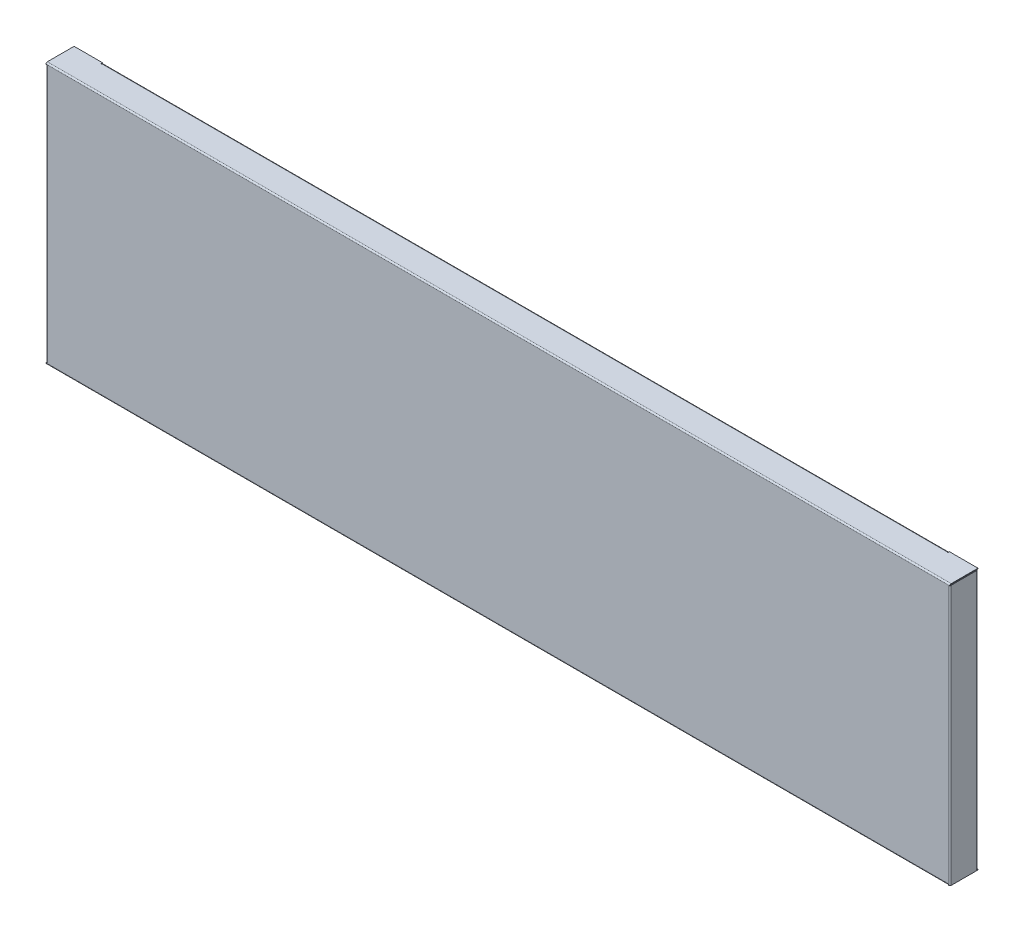
SolidWorks part; units mm, degrees
note: The reader was unsure of these and kept them because the rebuilt part matched: flange length of "Edge-Flange1", "Edge-Flange2", "Edge-Flange3", "Edge-Flange4", "Edge-Flange5", "Edge-Flange6", "Edge-Flange7", "Edge-Flange8".
ref_plane "Front Plane" through (0, 0, 0) normal (0, 0, 1) x (1, 0, 0)
ref_plane "Top Plane" through (0, 0, 0) normal (0, 1, 0) x (1, 0, 0)
ref_plane "Right Plane" through (0, 0, 0) normal (1, 0, 0) x (0, 0, -1)
sketch "Sketch1" plane through (0, 0, 0) normal (0, 0, 1) x (1, 0, 0)
  line L1 (-482.5, -139.5) -> (482.5, -139.5)
  line L2 (-482.5, -139.5) -> (-482.5, 139.5)
  line L3 (-482.5, 139.5) -> (482.5, 139.5)
  line L4 (482.5, -139.5) -> (482.5, 139.5)
  line L5 (-482.5, -139.5) -> (482.5, 139.5) construction
  line L6 (-482.5, 139.5) -> (482.5, -139.5) construction
  point P0 (0, 0)
  dimension "D1" = 965
  dimension "D2" = 279
base flange "Base-Flange1" sketch "Sketch1" thickness 0.7366 reverse thickness direction no parameters "D1"=0.7366
edge flange "Edge-Flange1" sketch "Sketch8" flange angle 90 flange length 30 flange position material inside bend radius 0.7366 thickness 0.7366 relief rectangular parameters "D6"=10
sketch "Sketch8" plane through (0, 139.5, -0.7366) normal (0, 1, 0) x (1, 0, 0)
  line L0 (482.5, 0) -> (-482.5, 0) construction
  line L1 (482.5, 0) -> (-482.5, 0)
  line L2 (-482.5, 0) -> (-482.5, 29.2634)
  line L3 (-482.5, 29.2634) -> (482.5, 29.2634)
  line L4 (482.5, 29.2634) -> (482.5, 0)
bend "EdgeBend1" bend radius 0.7366 bend angle 90 parameters "D5"=1
edge flange "Edge-Flange2" sketch "Sketch11" flange angle 90 flange length 30 flange position material inside bend radius 0.7366 thickness 0.7366 relief none parameters "D6"=10
sketch "Sketch11" plane through (482.5, 0, -0.7366) normal (1, 0, 0) x (0, -1, 0)
  line L0 (139.5, 0) -> (-138.0268, 0) construction
  line L1 (139.5, 0) -> (-138.0268, 0)
  line L2 (-138.0268, 0) -> (-138.0268, 29.2634)
  line L3 (-138.0268, 29.2634) -> (139.5, 29.2634)
  line L4 (139.5, 29.2634) -> (139.5, 0)
bend "EdgeBend2" bend radius 0.7366 bend angle 90 parameters "D5"=2
edge flange "Edge-Flange3" sketch "Sketch14" flange angle 90 flange length 30 flange position material inside bend radius 0.7366 thickness 0.7366 relief none parameters "D6"=10
sketch "Sketch14" plane through (0, -139.5, -0.7366) normal (0, -1, 0) x (-1, 0, 0)
  line L0 (482.5, 0) -> (-481.0268, 0) construction
  line L1 (482.5, 0) -> (-481.0268, 0)
  line L2 (-481.0268, 0) -> (-481.0268, 29.2634)
  line L3 (-481.0268, 29.2634) -> (482.5, 29.2634)
  line L4 (482.5, 29.2634) -> (482.5, 0)
bend "EdgeBend3" bend radius 0.7366 bend angle 90 parameters "D5"=3
edge flange "Edge-Flange4" sketch "Sketch17" flange angle 90 flange length 30 flange position material inside bend radius 0.7366 thickness 0.7366 relief none parameters "D6"=10
sketch "Sketch17" plane through (-482.5, 0, -0.7366) normal (-1, 0, 0) x (0, 1, 0)
  line L0 (138.0268, 0) -> (-138.0268, 0) construction
  line L1 (138.0268, 0) -> (-138.0268, 0)
  line L2 (-138.0268, 0) -> (-138.0268, 29.2634)
  line L3 (-138.0268, 29.2634) -> (138.0268, 29.2634)
  line L4 (138.0268, 29.2634) -> (138.0268, 0)
bend "EdgeBend4" bend radius 0.7366 bend angle 90 parameters "D5"=4
edge flange "Edge-Flange5" sketch "Sketch20" flange angle 90 flange length 30 flange position material inside bend radius 0.7366 thickness 0.7366 relief rectangular parameters "D6"=10
sketch "Sketch20" plane through (0, -138.7634, -30) normal (0, 0, -1) x (-1, 0, 0)
  line L0 (482.5, 0) -> (-481.0268, 0) construction
  line L1 (451.5634, 0) -> (-451.5634, 0)
  line L2 (-451.5634, 0) -> (-451.5634, 29.2634)
  line L3 (-451.5634, 29.2634) -> (451.5634, 29.2634)
  line L4 (451.5634, 29.2634) -> (451.5634, 0)
  line L5 (481.7634, 276.7902) -> (481.7634, 0.7366) construction
  line L6 (-481.7634, -0.7366) -> (-481.7634, 276.7902) construction
  dimension "D1" = 30.2
  dimension "D2" = 29.2634
  dimension "D3" = 30.2
bend "EdgeBend5" bend radius 0.7366 bend angle 90 parameters "D5"=5
edge flange "Edge-Flange6" sketch "Sketch23" flange angle 90 flange length 30 flange position material inside bend radius 0.7366 thickness 0.7366 relief rectangular parameters "D6"=10
sketch "Sketch23" plane through (0, 138.7634, -30) normal (0, 0, -1) x (1, 0, 0)
  line L0 (482.5, 0) -> (-482.5, 0) construction
  line L1 (451.5634, 0) -> (-451.5634, 0)
  line L2 (-451.5634, 0) -> (-451.5634, 29.2634)
  line L3 (-451.5634, 29.2634) -> (451.5634, 29.2634)
  line L4 (451.5634, 29.2634) -> (451.5634, 0)
  line L5 (-481.7634, 0.7366) -> (-481.7634, 276.7902) construction
  line L6 (481.7634, 278.2634) -> (481.7634, 0.7366) construction
  dimension "D1" = 30.2
  dimension "D2" = 30.2
bend "EdgeBend6" bend radius 0.7366 bend angle 90 parameters "D5"=6
edge flange "Edge-Flange7" sketch "Sketch26" flange angle 90 flange length 30 flange position material inside bend radius 0.7366 thickness 0.7366 relief rectangular parameters "D6"=10
sketch "Sketch26" plane through (481.7634, 0, -30) normal (0, 0, 1) x (0, 1, 0)
  line L1 (138.0268, 0) -> (-139.5, 0) construction
  line L2 (-138.5634, 0) -> (-138.5634, 29.2634)
  line L3 (-138.5634, 29.2634) -> (138.0634, 29.2634)
  line L4 (138.0634, 29.2634) -> (138.0634, 0)
  line L5 (138.0634, 0) -> (-138.5634, 0)
  line L6 (138.7634, -0.7366) -> (138.7634, 29.8317) construction
  line L7 (-138.7634, 29.8317) -> (-138.7634, 0.7366) construction
  dimension "D1" = 0.7
  dimension "D2" = 0.2
bend "EdgeBend7" bend radius 0.7366 bend angle 90 parameters "D5"=7
edge flange "Edge-Flange8" sketch "Sketch29" flange angle 90 flange length 30 flange position material inside bend radius 0.7366 thickness 0.7366 relief rectangular parameters "D6"=10
sketch "Sketch29" plane through (-481.7634, 0, -30) normal (0, 0, -1) x (0, 1, 0)
  line L0 (138.0268, 0) -> (-138.0268, 0) construction
  line L1 (138.0268, 0) -> (-138.0268, 0)
  line L2 (-138.0268, 0) -> (-138.0268, 29.2634)
  line L3 (-138.0268, 29.2634) -> (138.0268, 29.2634)
  line L4 (138.0268, 29.2634) -> (138.0268, 0)
bend "EdgeBend8" bend radius 0.7366 bend angle 90 parameters "D5"=8
sketch "Bend-Lines1" [suppressed] plane through (0, 0, 0) normal (0, 1, 0) x (1, 0, 0)
sketch "Bounding-Box1" [suppressed] plane through (0, 0, 0) normal (0, 1, 0) x (1, 0, 0)
sheet metal parameters "Sheet-Metal1" thickness 0.7366 parameters "D1"=0.7366
flat pattern "Flat-Pattern1" [suppressed]
sketch "Bend-Lines2" plane through (0, 0, 0) normal (0, 1, 0) x (1, 0, 0)
sketch3d "Bounding-Box2" [suppressed]
  line L0 (482.65, -190, 0) -> (-482.65, -190, 0) construction
  line L1 (482.65, 190, 0) -> (-482.65, 190, 0) construction
  line L2 (482.65, -190, 0) -> (482.65, 190, 0) construction
  line L3 (-482.65, -190, 0) -> (-482.65, 190, 0) construction
sheet metal parameters "Sheet-Metal2" thickness 0.7366 parameters "D1"=0.7366
flat pattern "Flat-Pattern1"
sketch "Bend-Lines2" plane through (0, 0, 0) normal (0, 0, 1) x (1, 0, 0)
  line L0 (482.65, 189.3946) -> (-482.65, 189.3946) construction
  line L1 (482.65, 189.3946) -> (-482.65, 189.3946) construction
sketch3d "Bounding-Box2" [suppressed]
  line L0 (-482.65, -190, 0) -> (482.65, -190, 0) construction
  line L1 (-482.65, 218.7892, 0) -> (482.65, 218.7892, 0) construction
  line L2 (-482.65, -190, 0) -> (-482.65, 218.7892, 0) construction
  line L3 (482.65, -190, 0) -> (482.65, 218.7892, 0) construction
bend of the flat pattern "Flatten-<EdgeBend1>1"
sheet metal parameters "Sheet-Metal3" thickness 0.7366 parameters "D1"=0.7366
flat pattern "Flat-Pattern1"
sketch "Bend-Lines2" plane through (0, 0, 0) normal (0, 0, 1) x (1, 0, 0)
  line L0 (482.65, 189.3946) -> (-482.65, 189.3946) construction
  line L1 (482.65, 189.3946) -> (-482.65, 189.3946) construction
  line L2 (482.0446, -190) -> (482.0446, 188.5268) construction
  line L3 (482.0446, -190) -> (482.0446, 188.5268) construction
sketch3d "Bounding-Box2" [suppressed]
  line L0 (-482.65, -190, 0) -> (511.4392, -190, 0) construction
  line L1 (-482.65, 218.7892, 0) -> (511.4392, 218.7892, 0) construction
  line L2 (-482.65, -190, 0) -> (-482.65, 218.7892, 0) construction
  line L3 (511.4392, -190, 0) -> (511.4392, 218.7892, 0) construction
bend of the flat pattern "Flatten-<EdgeBend1>1"
bend of the flat pattern "Flatten-<EdgeBend2>1"
sheet metal parameters "Sheet-Metal4" thickness 0.7366 parameters "D1"=0.7366
flat pattern "Flat-Pattern1"
sketch "Bend-Lines2" plane through (0, 0, 0) normal (0, 0, 1) x (1, 0, 0)
  line L0 (482.65, 189.3946) -> (-482.65, 189.3946) construction
  line L1 (482.65, 189.3946) -> (-482.65, 189.3946) construction
  line L2 (482.0446, -190) -> (482.0446, 188.5268) construction
  line L3 (482.0446, -190) -> (482.0446, 188.5268) construction
  line L4 (-482.65, -189.3946) -> (481.1768, -189.3946) construction
  line L5 (-482.65, -189.3946) -> (481.1768, -189.3946) construction
sketch3d "Bounding-Box2" [suppressed]
  line L0 (-482.65, -218.7892, 0) -> (511.4392, -218.7892, 0) construction
  line L1 (-482.65, 218.7892, 0) -> (511.4392, 218.7892, 0) construction
  line L2 (-482.65, -218.7892, 0) -> (-482.65, 218.7892, 0) construction
  line L3 (511.4392, -218.7892, 0) -> (511.4392, 218.7892, 0) construction
bend of the flat pattern "Flatten-<EdgeBend1>1"
bend of the flat pattern "Flatten-<EdgeBend2>1"
bend of the flat pattern "Flatten-<EdgeBend3>1"
sheet metal parameters "Sheet-Metal5" thickness 0.7366 parameters "D1"=0.7366
flat pattern "Flat-Pattern1"
sketch "Bend-Lines2" plane through (0, 0, 0) normal (0, 0, 1) x (1, 0, 0)
  line L0 (482.65, 189.3946) -> (-482.65, 189.3946) construction
  line L1 (482.65, 189.3946) -> (-482.65, 189.3946) construction
  line L2 (482.0446, -190) -> (482.0446, 188.5268) construction
  line L3 (482.0446, -190) -> (482.0446, 188.5268) construction
  line L4 (-482.65, -189.3946) -> (481.1768, -189.3946) construction
  line L5 (-482.65, -189.3946) -> (481.1768, -189.3946) construction
  line L6 (-482.0446, 188.5268) -> (-482.0446, -188.5268) construction
  line L7 (-482.0446, 188.5268) -> (-482.0446, -188.5268) construction
sketch3d "Bounding-Box2" [suppressed]
  line L0 (-511.4392, -218.7892, 0) -> (511.4392, -218.7892, 0) construction
  line L1 (-511.4392, 218.7892, 0) -> (511.4392, 218.7892, 0) construction
  line L2 (-511.4392, -218.7892, 0) -> (-511.4392, 218.7892, 0) construction
  line L3 (511.4392, -218.7892, 0) -> (511.4392, 218.7892, 0) construction
bend of the flat pattern "Flatten-<EdgeBend1>1"
bend of the flat pattern "Flatten-<EdgeBend2>1"
bend of the flat pattern "Flatten-<EdgeBend3>1"
bend of the flat pattern "Flatten-<EdgeBend4>1"
sheet metal parameters "Sheet-Metal6" thickness 0.7366 parameters "D1"=0.7366
flat pattern "Flat-Pattern1"
sketch "Bend-Lines2" plane through (0, 0, 0) normal (0, 0, 1) x (1, 0, 0)
  line L0 (482.65, 189.3946) -> (-482.65, 189.3946) construction
  line L1 (482.65, 189.3946) -> (-482.65, 189.3946) construction
  line L2 (482.0446, -190) -> (482.0446, 188.5268) construction
  line L3 (482.0446, -190) -> (482.0446, 188.5268) construction
  line L4 (-482.65, -189.3946) -> (481.1768, -189.3946) construction
  line L5 (-482.65, -189.3946) -> (481.1768, -189.3946) construction
  line L6 (-482.0446, 188.5268) -> (-482.0446, -188.5268) construction
  line L7 (-482.0446, 188.5268) -> (-482.0446, -188.5268) construction
  line L8 (-482.65, -218.1838) -> (481.1768, -218.1838) construction
  line L9 (-482.65, -218.1838) -> (481.1768, -218.1838) construction
sketch3d "Bounding-Box2" [suppressed]
  line L0 (-511.4392, -247.5783, 0) -> (511.4392, -247.5783, 0) construction
  line L1 (-511.4392, 218.7892, 0) -> (511.4392, 218.7892, 0) construction
  line L2 (-511.4392, -247.5783, 0) -> (-511.4392, 218.7892, 0) construction
  line L3 (511.4392, -247.5783, 0) -> (511.4392, 218.7892, 0) construction
bend of the flat pattern "Flatten-<EdgeBend1>1"
bend of the flat pattern "Flatten-<EdgeBend2>1"
bend of the flat pattern "Flatten-<EdgeBend3>1"
bend of the flat pattern "Flatten-<EdgeBend4>1"
bend of the flat pattern "Flatten-<EdgeBend5>1"
sheet metal parameters "Sheet-Metal7" thickness 0.7366 parameters "D1"=0.7366
flat pattern "Flat-Pattern1"
sketch "Bend-Lines2" plane through (0, 0, 0) normal (0, 0, 1) x (1, 0, 0)
  line L0 (482.65, 189.3946) -> (-482.65, 189.3946) construction
  line L1 (482.65, 189.3946) -> (-482.65, 189.3946) construction
  line L2 (482.0446, -190) -> (482.0446, 188.5268) construction
  line L3 (482.0446, -190) -> (482.0446, 188.5268) construction
  line L4 (-482.65, -189.3946) -> (481.1768, -189.3946) construction
  line L5 (-482.65, -189.3946) -> (481.1768, -189.3946) construction
  line L6 (-482.0446, 188.5268) -> (-482.0446, -188.5268) construction
  line L7 (-482.0446, 188.5268) -> (-482.0446, -188.5268) construction
  line L8 (-451.7134, -218.1838) -> (451.7134, -218.1838) construction
  line L9 (-451.7134, -218.1838) -> (451.7134, -218.1838) construction
  line L10 (451.7134, 218.1838) -> (-451.7134, 218.1838) construction
  line L11 (451.7134, 218.1838) -> (-451.7134, 218.1838) construction
sketch3d "Bounding-Box2" [suppressed]
  line L0 (-511.4392, -247.5783, 0) -> (511.4392, -247.5783, 0) construction
  line L1 (-511.4392, 247.5783, 0) -> (511.4392, 247.5783, 0) construction
  line L2 (-511.4392, -247.5783, 0) -> (-511.4392, 247.5783, 0) construction
  line L3 (511.4392, -247.5783, 0) -> (511.4392, 247.5783, 0) construction
bend of the flat pattern "Flatten-<EdgeBend1>1"
bend of the flat pattern "Flatten-<EdgeBend2>1"
bend of the flat pattern "Flatten-<EdgeBend3>1"
bend of the flat pattern "Flatten-<EdgeBend4>1"
bend of the flat pattern "Flatten-<EdgeBend5>1"
bend of the flat pattern "Flatten-<EdgeBend6>1"
sheet metal parameters "Sheet-Metal8" thickness 0.7366 parameters "D1"=0.7366
flat pattern "Flat-Pattern1"
sketch "Bend-Lines2" plane through (0, 0, 0) normal (0, 0, 1) x (1, 0, 0)
  line L0 (482.65, 189.3946) -> (-482.65, 189.3946) construction
  line L1 (482.65, 189.3946) -> (-482.65, 189.3946) construction
  line L2 (482.0446, -190) -> (482.0446, 188.5268) construction
  line L3 (482.0446, -190) -> (482.0446, 188.5268) construction
  line L4 (-482.65, -189.3946) -> (481.1768, -189.3946) construction
  line L5 (-482.65, -189.3946) -> (481.1768, -189.3946) construction
  line L6 (-482.0446, 188.5268) -> (-482.0446, -188.5268) construction
  line L7 (-482.0446, 188.5268) -> (-482.0446, -188.5268) construction
  line L8 (-451.7134, -218.1838) -> (451.7134, -218.1838) construction
  line L9 (-451.7134, -218.1838) -> (451.7134, -218.1838) construction
  line L10 (451.7134, 218.1838) -> (-451.7134, 218.1838) construction
  line L11 (451.7134, 218.1838) -> (-451.7134, 218.1838) construction
  line L12 (510.8338, -189.0634) -> (510.8338, 188.5268) construction
  line L13 (510.8338, -189.0634) -> (510.8338, 188.5268) construction
sketch3d "Bounding-Box2" [suppressed]
  line L0 (-511.4392, -247.5783, 0) -> (540.2283, -247.5783, 0) construction
  line L1 (-511.4392, 247.5783, 0) -> (540.2283, 247.5783, 0) construction
  line L2 (-511.4392, -247.5783, 0) -> (-511.4392, 247.5783, 0) construction
  line L3 (540.2283, -247.5783, 0) -> (540.2283, 247.5783, 0) construction
bend of the flat pattern "Flatten-<EdgeBend1>1"
bend of the flat pattern "Flatten-<EdgeBend2>1"
bend of the flat pattern "Flatten-<EdgeBend3>1"
bend of the flat pattern "Flatten-<EdgeBend4>1"
bend of the flat pattern "Flatten-<EdgeBend5>1"
bend of the flat pattern "Flatten-<EdgeBend6>1"
bend of the flat pattern "Flatten-<EdgeBend7>1"
sheet metal parameters "Sheet-Metal9" thickness 0.7366 parameters "D1"=0.7366
flat pattern "Flat-Pattern1"
sketch "Bend-Lines2" plane through (0, 0, 0) normal (0, 0, 1) x (1, 0, 0)
  line L0 (482.5, 138.8946) -> (-482.5, 138.8946) construction
  line L1 (482.5, 138.8946) -> (-482.5, 138.8946) construction
  line L2 (481.8946, -139.5) -> (481.8946, 138.0268) construction
  line L3 (481.8946, -139.5) -> (481.8946, 138.0268) construction
  line L4 (-482.5, -138.8946) -> (481.0268, -138.8946) construction
  line L5 (-482.5, -138.8946) -> (481.0268, -138.8946) construction
  line L6 (-481.8946, 138.0268) -> (-481.8946, -138.0268) construction
  line L7 (-481.8946, 138.0268) -> (-481.8946, -138.0268) construction
  line L8 (-451.5634, -167.6838) -> (451.5634, -167.6838) construction
  line L9 (-451.5634, -167.6838) -> (451.5634, -167.6838) construction
  line L10 (451.5634, 167.6838) -> (-451.5634, 167.6838) construction
  line L11 (451.5634, 167.6838) -> (-451.5634, 167.6838) construction
  line L12 (510.6838, -138.5634) -> (510.6838, 138.0268) construction
  line L13 (510.6838, -138.5634) -> (510.6838, 138.0268) construction
  line L14 (-510.6838, 138.0268) -> (-510.6838, -138.0268) construction
  line L15 (-510.6838, 138.0268) -> (-510.6838, -138.0268) construction
sketch3d "Bounding-Box2" [suppressed]
  line L0 (-540.0783, -197.0783, 0) -> (540.0783, -197.0783, 0) construction
  line L1 (-540.0783, 197.0783, 0) -> (540.0783, 197.0783, 0) construction
  line L2 (-540.0783, -197.0783, 0) -> (-540.0783, 197.0783, 0) construction
  line L3 (540.0783, -197.0783, 0) -> (540.0783, 197.0783, 0) construction
bend of the flat pattern "Flatten-<EdgeBend1>1"
bend of the flat pattern "Flatten-<EdgeBend2>1"
bend of the flat pattern "Flatten-<EdgeBend3>1"
bend of the flat pattern "Flatten-<EdgeBend4>1"
bend of the flat pattern "Flatten-<EdgeBend5>1"
bend of the flat pattern "Flatten-<EdgeBend6>1"
bend of the flat pattern "Flatten-<EdgeBend7>1"
bend of the flat pattern "Flatten-<EdgeBend8>1"
